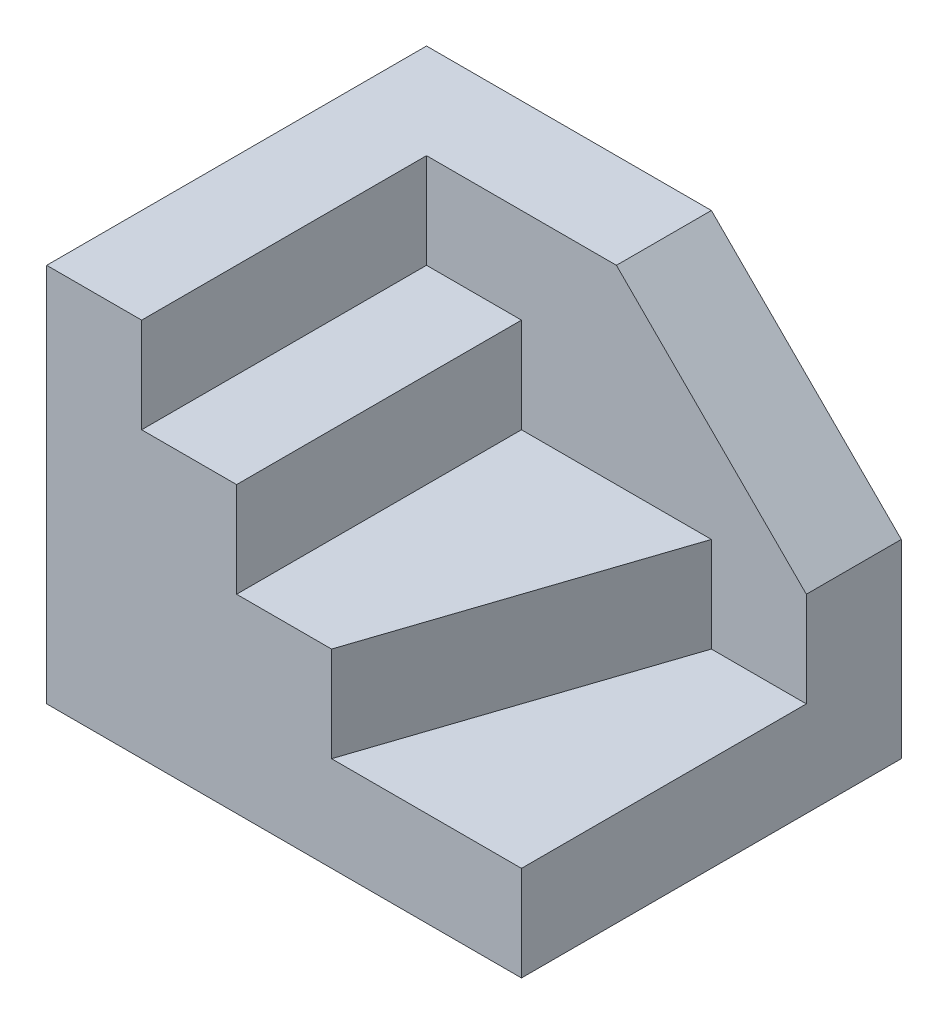
SolidWorks part; units mm, degrees
ref_plane "前基準面" through (0, 0, 0) normal (0, 0, 1) x (1, 0, 0)
ref_plane "上基準面" through (0, 0, 0) normal (0, 1, 0) x (1, 0, 0)
ref_plane "右基準面" through (0, 0, 0) normal (1, 0, 0) x (0, 0, -1)
sketch "草圖1" plane through (0, 0, 0) normal (0, 1, 0) x (1, 0, 0)
  line L0 (12.5, 5) -> (-7.5, 5)
  line L1 (12.5, -10) -> (-12.5, -10)
  line L2 (12.5, -10) -> (12.5, 10)
  line L3 (12.5, 10) -> (-12.5, 10)
  line L4 (-12.5, -10) -> (-12.5, 10)
  line L5 (12.5, -10) -> (-12.5, 10) construction
  line L6 (12.5, 10) -> (-12.5, -10) construction
  line L7 (-7.5, 5) -> (-7.5, -10)
  line L8 (-7.5, -10) -> (-2.5, -10)
  line L9 (-2.5, -10) -> (-2.5, 5)
  line L10 (-2.5, 5) -> (7.5, 5)
  line L11 (7.5, 5) -> (2.5, -10)
  point P0 (0, 0)
  dimension "D1" = 20
  dimension "D2" = 25
  dimension "D3" = 5
  dimension "D4" = 5
  dimension "D5" = 5
  dimension "D6" = 5
  dimension "D7" = 10
extrude "填料-伸長1" add sketch "草圖1" along normal blind 5 contours L7 L0 L2 L3 L4 L1 | L1 L9 L0 L7 | L11 L0 L9 L1 | L0 L11 L1 L2 region at (8.6111, 0, 3.3333) region at (10, 0, -5.3202) region at (1.3889, 0, 1.6667) region at (-5, 0, 2.5)
extrude "填料-伸長2" add sketch "草圖1<3>" along normal blind 10 contours L11 L0 L9 L1 region at (1.3889, 0, 1.6667)
sketch "草圖1<3>" plane through (0, 0, 0) normal (0, 1, 0) x (1, 0, 0) same geometry as "草圖1"
extrude "填料-伸長3" add sketch "草圖1<4>" along normal blind 15 contours L1 L9 L0 L7 region at (-5, 0, 2.5)
sketch "草圖1<4>" plane through (0, 0, 0) normal (0, 1, 0) x (1, 0, 0) same geometry as "草圖1"
extrude "填料-伸長4" add sketch "草圖1<5>" along normal blind 20 contours L7 L0 L2 L3 L4 L1 region at (10, 0, -5.3202)
sketch "草圖1<5>" plane through (0, 0, 0) normal (0, 1, 0) x (1, 0, 0) same geometry as "草圖1"
sketch "草圖2" plane through (0, 0, -5) normal (0, 0, 1) x (1, 0, 0)
  line L0 (12.5, 20) -> (2.5, 20)
  line L1 (12.5, 20) -> (-7.5, 20) construction
  line L2 (2.5, 20) -> (12.5, 10)
  line L3 (12.5, 20) -> (12.5, 5) construction
  line L4 (12.5, 10) -> (12.5, 20)
  dimension "D1" = 10
  dimension "D2" = 10
extrude "除料-伸長1" cut sketch "草圖2" against normal blind 20
